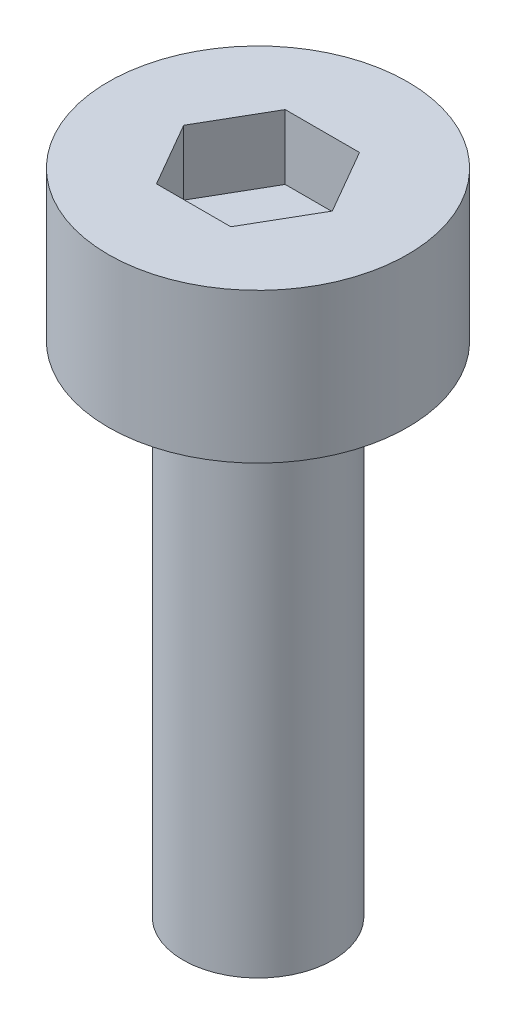
SolidWorks part; units mm, degrees
ref_plane "Front Plane" through (0, 0, 0) normal (0, 0, 1) x (1, 0, 0)
ref_plane "Top Plane" through (0, 0, 0) normal (0, 1, 0) x (1, 0, 0)
ref_plane "Right Plane" through (0, 0, 0) normal (1, 0, 0) x (0, 0, -1)
sketch "Sketch1" plane through (0, 0, 0) normal (0, 1, 0) x (1, 0, 0)
  circle A0 centre (0, 0) radius 1.5
  dimension "D1" = 3
extrude "ScrewShaft" add sketch "Sketch1" along normal blind 10
sketch "Sketch2" plane through (0, 10, 0) normal (0, 1, 0) x (1, 0, 0)
  circle A0 centre (0, 0) radius 3
  dimension "D1" = 6
extrude "Boss-Extrude2" add sketch "Sketch2" along normal blind 3
sketch "Sketch3" plane through (0, 13, 0) normal (0, 1, 0) x (1, 0, 0)
  line L0 (0, 0) -> (0, 1.29) construction
  line L1 (1.4896, 0) -> (0.7448, 1.29)
  line L2 (0.7448, 1.29) -> (-0.7448, 1.29)
  line L3 (-0.7448, 1.29) -> (-1.4896, 0)
  line L4 (-1.4896, 0) -> (-0.7448, -1.29)
  line L5 (-0.7448, -1.29) -> (0.7448, -1.29)
  line L6 (0.7448, -1.29) -> (1.4896, 0)
  circle A0 centre (0, 0) radius 1.29 construction
  dimension "D1" = 2.58
extrude "Cut-Extrude1" cut sketch "Sketch3" against normal blind 1.3
equation "\"X-ROD-SPACING\"=45"
equation "\"Y-ROD-SPACING\"=75"
equation "\"Z-ROD-SPACING\"=17.5"
equation "\"Y-BED-OFFSET\"=2"
equation "\"Y-BED-ROD-INSET\"=3.5"
equation "\"T-SLOT-NUT-FILLET-RADIUS\"=0.5"
equation "\"T-SLOT-SCREW-SHAFT-RADIUS\"=1.55"
equation "\"T-SLOT-SCREW-SHAFT-CUTOUT-LENGTH\"=11.0"
equation "\"T-SLOT-NUT-DEPTH\"=3.5"
equation "\"T-SLOT-NUT-WIDTH\"=2.85"
equation "\"T-SLOT-NUT-END-DISTANCE\"=8"
equation "\"ACRYLIC-THICKNESS\"=10"
equation "\"ACRYLIC-THICKNESS2\"=4.5"
equation "\"ACRYLIC-TAB-CUTOUT-SIZE\"=\"ACRYLIC-THICKNESS\"+\"ACRYLIC-TAB-TOLERANCE\"*2"
equation "\"ACRYLIC-TAB-WIDTH\"=\"ACRYLIC-THICKNESS\""
equation "\"ACRYLIC-M3-HOLE\"=2.9"
equation "\"SMOOTHROD-CAP-SCREW-DISTANCE\"=20"
equation "\"FRAME-WIDTH-INNER\"=370"
equation "\"NEMA17-HOLE-SPACING\"=31"
equation "\"NEMA17-CENTRAL-CUTOUT\"=22.5"
equation "\"Z-BRACKET-REACH\"=55"
equation "\"TOP-BRACKET-SPACING\"=40"
equation "\"SMOOTHROD-X-LENGTH\"=350"
equation "\"SMOOTHROD-Y-LENGTH\"=350"
equation "\"SMOOTHROD-Z-LENGTH\"=350"
equation "\"SMOOTHROD-TIGHTENING-HEADROOM\"=.25"
equation "\"LEADSCREW-Z-LENGTH\"=300"
equation "\"SCREW-LENGTH-FRAME\"=\"ACRYLIC-THICKNESS\" + 10"
equation "\"SCREW-HEAD-RADIUS\"=6"
equation "\"PRINTED-X-SMOOTHROD-DIAMETER\"=8.4"
equation "\"PRINTED-X-SMOOTHROD-CUTOUT\"=10"
equation "\"PRINTED-X-BASE-HEIGHT\"=10"
equation "\"PRINTED-LM8UU-CUTOUT-SIZE\"=15.5"
equation "\"PRINTED-LM8UU-CUTOUT-LENGTH\"=24.5"
equation "\"PRINTED-X-IDLER-HEIGHT\"=16"
equation "\"PSU-MOUNTING-WIDTH\"=95"
equation "\"PSU-MOUNTING-HEIGHT\"=177"
equation "\"D1@Sketch2\"=\"SCREW-HEAD-RADIUS\""
